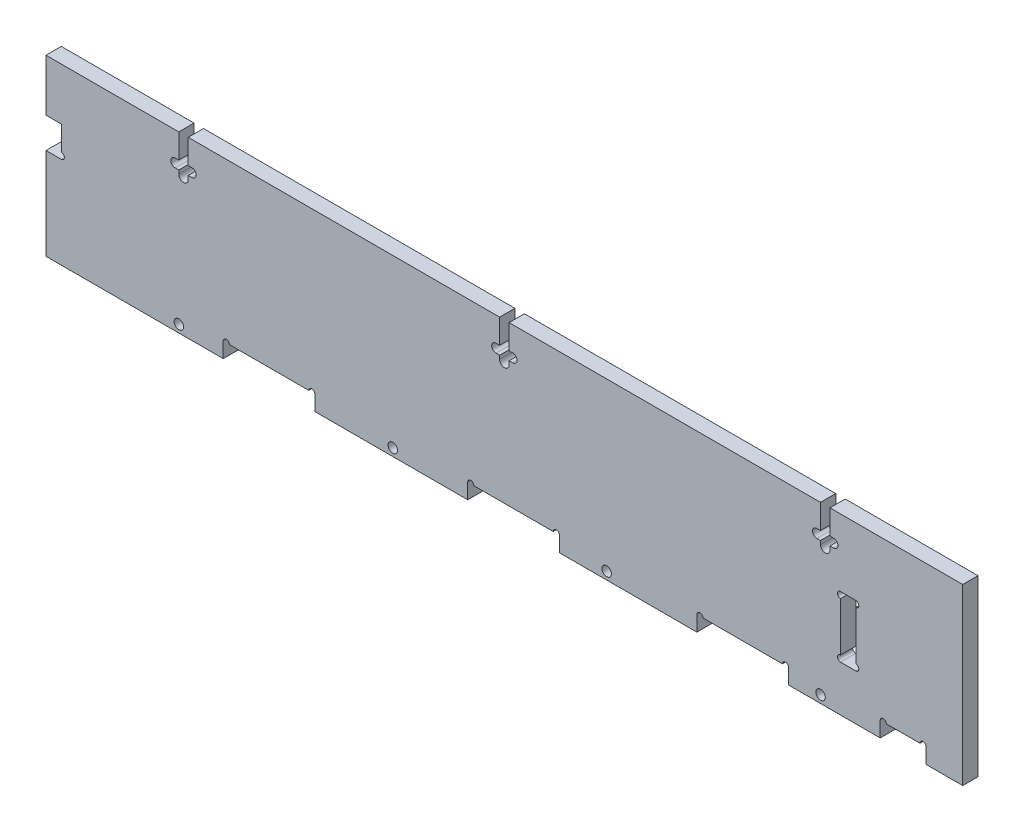
SolidWorks part; units mm, degrees
material "사용자정의 플라스틱"
ref_plane "정면" through (0, 0, 0) normal (0, 0, 1) x (1, 0, 0)
ref_plane "윗면" through (0, 0, 0) normal (0, 1, 0) x (1, 0, 0)
ref_plane "우측면" through (0, 0, 0) normal (1, 0, 0) x (0, 0, -1)
sketch "스케치1" plane through (0, 0, 0) normal (0, 0, 1) x (1, 0, 0)
  line L1 (0, 0) -> (300, 0)
  line L2 (0, 0) -> (0, 57)
  line L3 (0, 57) -> (300, 57)
  line L4 (300, 0) -> (300, 57)
  dimension "D1" = 57
  dimension "D2" = 300
extrude "보스-돌출1" add sketch "스케치1" along normal blind 5
sketch "스케치2" plane through (0, 0, 5) normal (0, 0, 1) x (1, 0, 0)
  line L0 (0, 57) -> (0, 0) construction
  line L1 (5, 40) -> (0, 40)
  line L2 (5, 40) -> (5, 30)
  line L3 (5, 30) -> (0, 30)
  line L4 (0, 40) -> (0, 30)
  line L5 (5, 30) -> (0, 30) construction
  line L6 (0, 0) -> (300, 0) construction
  line L7 (58, 5) -> (88, 5)
  line L8 (58, 5) -> (58, 0)
  line L9 (58, 0) -> (88, 0)
  line L10 (88, 5) -> (88, 0)
  line L11 (88, 5) -> (88, 0) construction
  line L12 (168, 5) -> (168, 0) construction
  line L13 (168, 0) -> (138, 0)
  line L14 (168, 0) -> (168, 5)
  line L15 (168, 5) -> (138, 5)
  line L16 (138, 0) -> (138, 5)
  line L17 (243, 5) -> (243, 0) construction
  line L18 (243, 0) -> (213, 0)
  line L19 (243, 0) -> (243, 5)
  line L20 (243, 5) -> (213, 5)
  line L21 (213, 0) -> (213, 5)
  line L22 (288, 5) -> (288, 0) construction
  line L23 (288, 0) -> (273, 0)
  line L24 (288, 0) -> (288, 5)
  line L25 (288, 5) -> (273, 5)
  line L26 (273, 0) -> (273, 5)
  line L28 (260, 35) -> (265, 35)
  line L29 (260, 35) -> (260, 15)
  line L30 (260, 15) -> (265, 15)
  line L31 (265, 35) -> (265, 15)
extrude "컷-돌출1" cut sketch "스케치2" against normal blind 5
sketch "스케치3" plane through (0, 0, 5) normal (0, 0, 1) x (1, 0, 0)
  line L0 (265, 35) -> (260, 35) construction
  line L1 (260, 15) -> (265, 15) construction
  line L4 (243, 5) -> (213, 5) construction
  line L5 (88, 5) -> (58, 5) construction
  line L6 (168, 5) -> (138, 5) construction
  line L7 (5, 30) -> (5, 40) construction
  line L8 (288, 5) -> (273, 5) construction
  line L9 (273, 5) -> (273, 0) construction
  line L10 (288, 0) -> (288, 5) construction
  circle A0 centre (274, 5) radius 1
  circle A1 centre (287, 5) radius 1
  circle A2 centre (260, 16) radius 1
  circle A3 centre (265, 16) radius 1
  circle A4 centre (265, 34) radius 1
  circle A5 centre (260, 34) radius 1
  circle A6 centre (214, 5) radius 1
  circle A7 centre (242, 5) radius 1
  circle A8 centre (87, 5) radius 1
  circle A9 centre (139, 5) radius 1
  circle A10 centre (167, 5) radius 1
  circle A11 centre (5, 31) radius 1
  circle A13 centre (59, 5) radius 1
  dimension "D1" = 2
  dimension "D2" = 2
extrude "컷-돌출2" cut sketch "스케치3" against normal blind 5
sketch "스케치4" plane through (0, 0, 0) normal (0, 0, -1) x (-1, 0, 0)
  line L0 (-45.0287, 2.5) -> (-41.9287, 2.5) construction
  line L3 (-45.0287, 5) -> (-45.0287, 0) construction
  line L6 (-41.9287, 5) -> (-41.9287, 0) construction
  line L9 (-115.0287, 2.5) -> (-111.9287, 2.5) construction
  line L10 (-115.0287, 5) -> (-115.0287, 0) construction
  line L11 (-111.9287, 5) -> (-111.9287, 0) construction
  line L12 (-185.0287, 2.5) -> (-181.9287, 2.5) construction
  line L13 (-185.0287, 5) -> (-185.0287, 0) construction
  line L14 (-181.9287, 5) -> (-181.9287, 0) construction
  line L15 (-255.0287, 2.5) -> (-251.9287, 2.5) construction
  line L16 (-255.0287, 5) -> (-255.0287, 0) construction
  line L17 (-251.9287, 5) -> (-251.9287, 0) construction
  circle A0 centre (-253.4787, 2.5) radius 1.55
  circle A1 centre (-183.4787, 2.5) radius 1.55
  circle A2 centre (-113.4787, 2.5) radius 1.55
  circle A3 centre (-43.4787, 2.5) radius 1.55
extrude "컷-돌출3" cut sketch "스케치4" against normal blind 10
sketch "스케치5" plane through (0, 0, 5) normal (0, 0, 1) x (1, 0, 0)
  line L0 (43.45, 57) -> (43.45, 49)
  line L1 (46.55, 45) -> (43.45, 45) construction
  line L2 (47.75, 49) -> (47.75, 46.2) construction
  line L3 (43.45, 49) -> (43.45, 46.2) construction
  line L4 (46.55, 57) -> (43.45, 57)
  line L5 (47.75, 46.2) -> (46.55, 46.2)
  line L6 (46.55, 57) -> (46.55, 49)
  line L7 (42.25, 46.2) -> (42.25, 49) construction
  line L8 (46.55, 49) -> (47.75, 49)
  line L9 (46.55, 46.2) -> (46.55, 49) construction
  line L10 (43.45, 46.2) -> (43.45, 45)
  line L11 (46.55, 49) -> (43.45, 49) construction
  line L12 (46.55, 46.2) -> (43.45, 46.2) construction
  line L13 (43.45, 46.2) -> (42.25, 46.2)
  line L14 (46.55, 46.2) -> (46.55, 45)
  line L15 (45, 45) -> (45, 43.45) construction
  line L16 (42.25, 49) -> (43.45, 49)
  line L17 (47.75, 47.6) -> (46.55, 47.6) construction
  line L18 (42.25, 47.6) -> (43.45, 47.6) construction
  line L19 (45, 46.2) -> (45, 45) construction
  line L20 (42.25, 47.6) -> (40.85, 47.6) construction
  line L21 (47.75, 47.6) -> (49.15, 47.6) construction
  line L22 (0, 57) -> (45, 57) construction
  line L23 (300, 57) -> (0, 57) construction
  line L24 (45, 57) -> (150, 57) construction
  line L25 (150, 57) -> (255, 57) construction
  line L26 (255, 57) -> (300, 57) construction
  line L49 (151.55, 49) -> (152.75, 49)
  line L50 (151.55, 49) -> (148.45, 49) construction
  line L51 (148.45, 46.2) -> (148.45, 45)
  line L52 (147.25, 46.2) -> (147.25, 49) construction
  line L53 (148.45, 57) -> (148.45, 49)
  line L54 (151.55, 57) -> (151.55, 49)
  line L55 (151.55, 46.2) -> (151.55, 45)
  line L56 (150, 46.2) -> (150, 45) construction
  line L57 (151.55, 46.2) -> (151.55, 49) construction
  line L58 (152.75, 47.6) -> (154.15, 47.6) construction
  line L59 (152.75, 46.2) -> (151.55, 46.2)
  line L60 (148.45, 49) -> (148.45, 46.2) construction
  line L61 (147.25, 47.6) -> (145.85, 47.6) construction
  line L62 (151.55, 57) -> (148.45, 57)
  line L63 (148.45, 46.2) -> (147.25, 46.2)
  line L64 (151.55, 46.2) -> (148.45, 46.2) construction
  line L65 (151.55, 45) -> (148.45, 45) construction
  line L66 (147.25, 47.6) -> (148.45, 47.6) construction
  line L67 (147.25, 49) -> (148.45, 49)
  line L68 (152.75, 49) -> (152.75, 46.2) construction
  line L69 (150, 45) -> (150, 43.45) construction
  line L70 (152.75, 47.6) -> (151.55, 47.6) construction
  line L71 (256.55, 49) -> (257.75, 49)
  line L72 (256.55, 49) -> (253.45, 49) construction
  line L73 (253.45, 46.2) -> (253.45, 45)
  line L74 (252.25, 46.2) -> (252.25, 49) construction
  line L75 (253.45, 57) -> (253.45, 49)
  line L76 (256.55, 57) -> (256.55, 49)
  line L77 (256.55, 46.2) -> (256.55, 45)
  line L78 (255, 46.2) -> (255, 45) construction
  line L79 (256.55, 46.2) -> (256.55, 49) construction
  line L80 (257.75, 47.6) -> (259.15, 47.6) construction
  line L81 (257.75, 46.2) -> (256.55, 46.2)
  line L82 (253.45, 49) -> (253.45, 46.2) construction
  line L83 (252.25, 47.6) -> (250.85, 47.6) construction
  line L84 (256.55, 57) -> (253.45, 57)
  line L85 (253.45, 46.2) -> (252.25, 46.2)
  line L86 (256.55, 46.2) -> (253.45, 46.2) construction
  line L87 (256.55, 45) -> (253.45, 45) construction
  line L88 (252.25, 47.6) -> (253.45, 47.6) construction
  line L89 (252.25, 49) -> (253.45, 49)
  line L90 (257.75, 49) -> (257.75, 46.2) construction
  line L91 (255, 45) -> (255, 43.45) construction
  line L92 (257.75, 47.6) -> (256.55, 47.6) construction
  arc A0 (43.45, 45) -> (46.55, 45) centre (45, 45) ccw
  arc A1 (47.75, 46.2) -> (47.75, 49) centre (47.75, 47.6) ccw
  arc A2 (42.25, 49) -> (42.25, 46.2) centre (42.25, 47.6) ccw
  arc A6 (152.75, 46.2) -> (152.75, 49) centre (152.75, 47.6) ccw
  arc A7 (147.25, 49) -> (147.25, 46.2) centre (147.25, 47.6) ccw
  arc A8 (148.45, 45) -> (151.55, 45) centre (150, 45) ccw
  arc A9 (257.75, 46.2) -> (257.75, 49) centre (257.75, 47.6) ccw
  arc A10 (252.25, 49) -> (252.25, 46.2) centre (252.25, 47.6) ccw
  arc A11 (253.45, 45) -> (256.55, 45) centre (255, 45) ccw
  dimension "D1" = 3.1
  dimension "D2" = 5.5
  dimension "D3" = 2.8
  dimension "D4" = 1.2
  dimension "D5" = 8
  dimension "D6" = 3.1
  dimension "D7" = 45
  dimension "D14" = 3.1
  dimension "D15" = 5.5
  dimension "D16" = 2.8
  dimension "D17" = 1.2
  dimension "D18" = 8
  dimension "D19" = 3.1
  dimension "D20" = 3.1
  dimension "D21" = 5.5
  dimension "D22" = 2.8
  dimension "D23" = 1.2
  dimension "D24" = 8
  dimension "D25" = 3.1
extrude "컷-돌출4" cut sketch "스케치5" against normal blind 10
